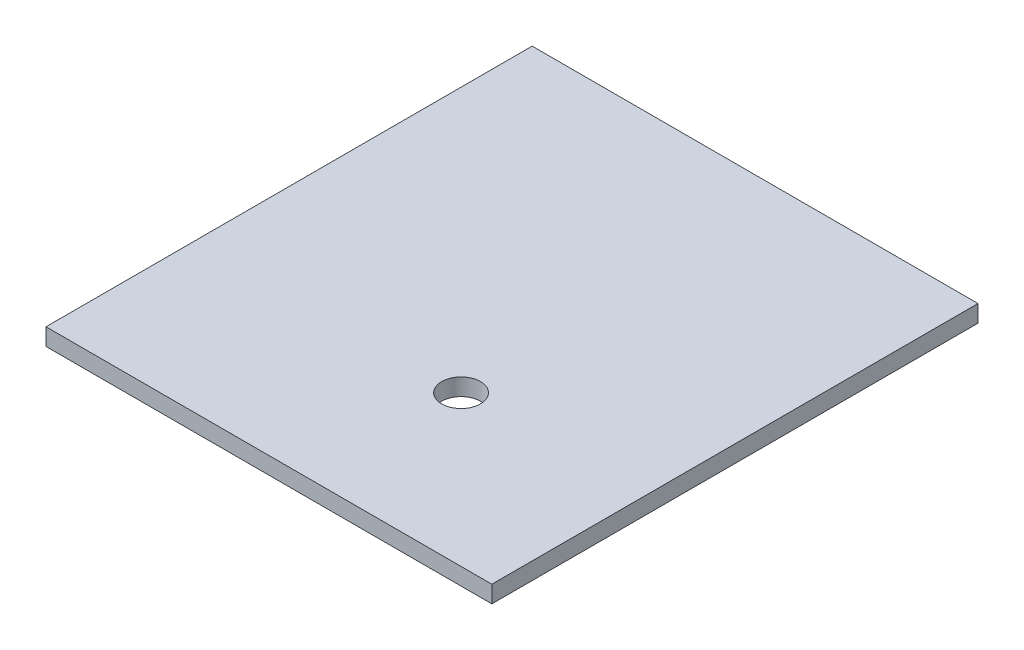
SolidWorks part; units mm, degrees
ref_plane "Front Plane" through (0, 0, 0) normal (0, 0, 1) x (1, 0, 0)
ref_plane "Top Plane" through (0, 0, 0) normal (0, 1, 0) x (1, 0, 0)
ref_plane "Right Plane" through (0, 0, 0) normal (1, 0, 0) x (0, 0, -1)
sketch "Sketch1" plane through (0, 0, 0) normal (0, 1, 0) x (1, 0, 0)
  line L1 (-73.025, -79.629) -> (73.025, -79.629)
  line L2 (-73.025, -79.629) -> (-73.025, 79.629)
  line L3 (-73.025, 79.629) -> (73.025, 79.629)
  line L4 (73.025, -79.629) -> (73.025, 79.629)
  line L5 (-73.025, -79.629) -> (73.025, 79.629) construction
  line L6 (-73.025, 79.629) -> (73.025, -79.629) construction
  point P0 (0, 0)
  point P6 (0, 0)
  point P7 (0, 0)
  point P8 (0, 0)
  point P9 (0, 0)
  point P17 (0, 0)
  dimension "D1" = 146.05
  dimension "D2" = 159.258
extrude "Boss-Extrude1" add sketch "Sketch1" along normal blind 5.588
sketch "Sketch4" plane through (0, 5.588, 0) normal (0, 1, 0) x (1, 0, 0)
  line L0 (-73.025, -79.629) -> (73.025, -79.629) construction
  line L1 (73.025, -79.629) -> (73.025, 79.629) construction
  circle A4 centre (13.6706, -30.353) radius 6.35
  point P0 (0, 0)
  point P4 (0, 0)
  point P14 (0, 0)
  dimension "D1" = 12.7
  dimension "D2" = 49.276
  dimension "D3" = 59.3544
extrude "Cut-Extrude1" cut sketch "Sketch4" against normal up to next
